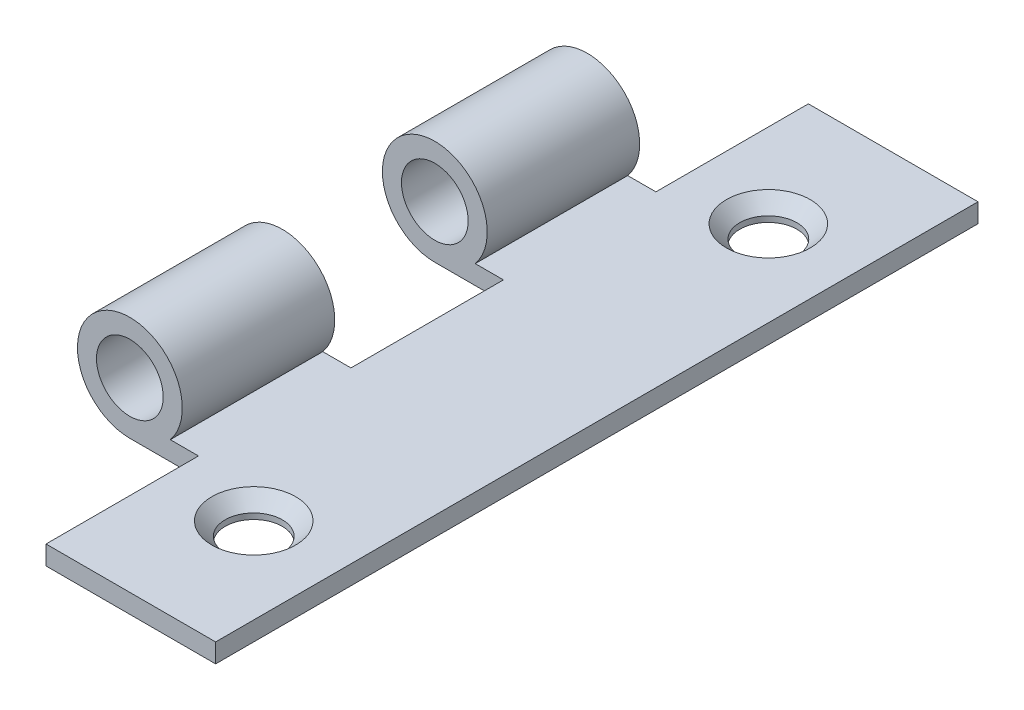
SolidWorks part; units mm, degrees
ref_plane "Plan de face" through (0, 0, 0) normal (0, 0, 1) x (1, 0, 0)
ref_plane "Plan de dessus" through (0, 0, 0) normal (0, 1, 0) x (1, 0, 0)
ref_plane "Plan de droite" through (0, 0, 0) normal (1, 0, 0) x (0, 0, -1)
sketch "Esquisse1" plane through (0, 0, 0) normal (0, 0, 1) x (1, 0, 0)
  line L0 (12.5, -1.75) -> (2.1213, -1.75)
  line L1 (12.5, -1.75) -> (12.5, -2.75)
  line L2 (12.5, -2.75) -> (0, -2.75)
  circle A0 centre (0, 0) radius 1.75
  arc A2 (2.1213, -1.75) -> (0, -2.75) centre (0, 0) ccw
  dimension "D2" = 2.75
  dimension "D1" = 1
  dimension "D3" = 12.5
extrude "Boss.-Extru.1" add sketch "Esquisse1" along normal blind 40
sketch "Esquisse2" plane through (0, -1.75, 0) normal (0, 1, 0) x (1, 0, 0)
  line L1 (-14.2, -16) -> (3.6, -16)
  line L2 (-14.2, -16) -> (-14.2, -24)
  line L3 (-14.2, -24) -> (3.6, -24)
  line L4 (3.6, -16) -> (3.6, -24)
  line L5 (-14.2, -32) -> (3.6, -32)
  line L6 (-14.2, -32) -> (-14.2, -40)
  line L7 (-14.2, -40) -> (3.6, -40)
  line L8 (3.6, -32) -> (3.6, -40)
  line L11 (12.5, -40) -> (12.5, 0) construction
  line L12 (-14.2, 0) -> (3.6, 0)
  line L13 (-14.2, 0) -> (-14.2, -8)
  line L14 (-14.2, -8) -> (3.6, -8)
  line L15 (3.6, 0) -> (3.6, -8)
  line L17 (12.5, 0) -> (2.1213, 0) construction
  dimension "D1" = 8
  dimension "D2" = 8
  dimension "D3" = 8
  dimension "D4" = 8.9
  dimension "D5" = 8
  dimension "D6" = 8
extrude "Enlèv. mat.-Extru.3" cut sketch "Esquisse2" against normal blind 20 and the other way blind 20
hole_wizard "Dégagement M31" positions "Esquisse4" profile "Esquisse3" hole size "M3" standard "Ansi Metric"
sketch "Esquisse4" plane through (0, -1.75, 0) normal (0, 1, 0) x (1, 0, 0)
  line L0 (12.5, -40) -> (12.5, 0) construction
  line L1 (12.5, -40) -> (3.6, -40) construction
  line L2 (12.5, 0) -> (3.6, 0) construction
  point P0 (8, -33.5)
  point P2 (8, -6.5)
  dimension "D1" = 4.5
  dimension "D2" = 4.5
  dimension "D3" = 6.5
  dimension "D4" = 6.5
sketch "Esquisse3" plane through (8, -1.75, 33.5) normal (1, 0, 0) x (0, 0, 1)
  line L0 (0, 0) -> (0, 10.9013)
  line L1 (0, 10.9013) -> (1.5, 10)
  line L2 (1.5, 10) -> (1.5, 0.7)
  line L3 (1.5, 0.7) -> (2.2, 0)
  line L5 (2.2, 0) -> (0, 0)
  line L6 (-1.5, 0.7) -> (-2.2, 0) construction
  line L10 (0, 10.9013) -> (-1.5, 10) construction
  line L11 (0, -6.35) -> (0, 107.95) construction
  dimension "Diamètre du perçage" = 3
  dimension "Profondeur du perçage" = 10
  dimension "Diamètre du fraisage entrant" = 4.4
  dimension "Angle du fraisage entrant" = 90
  dimension "Angle de pointe" = 118
